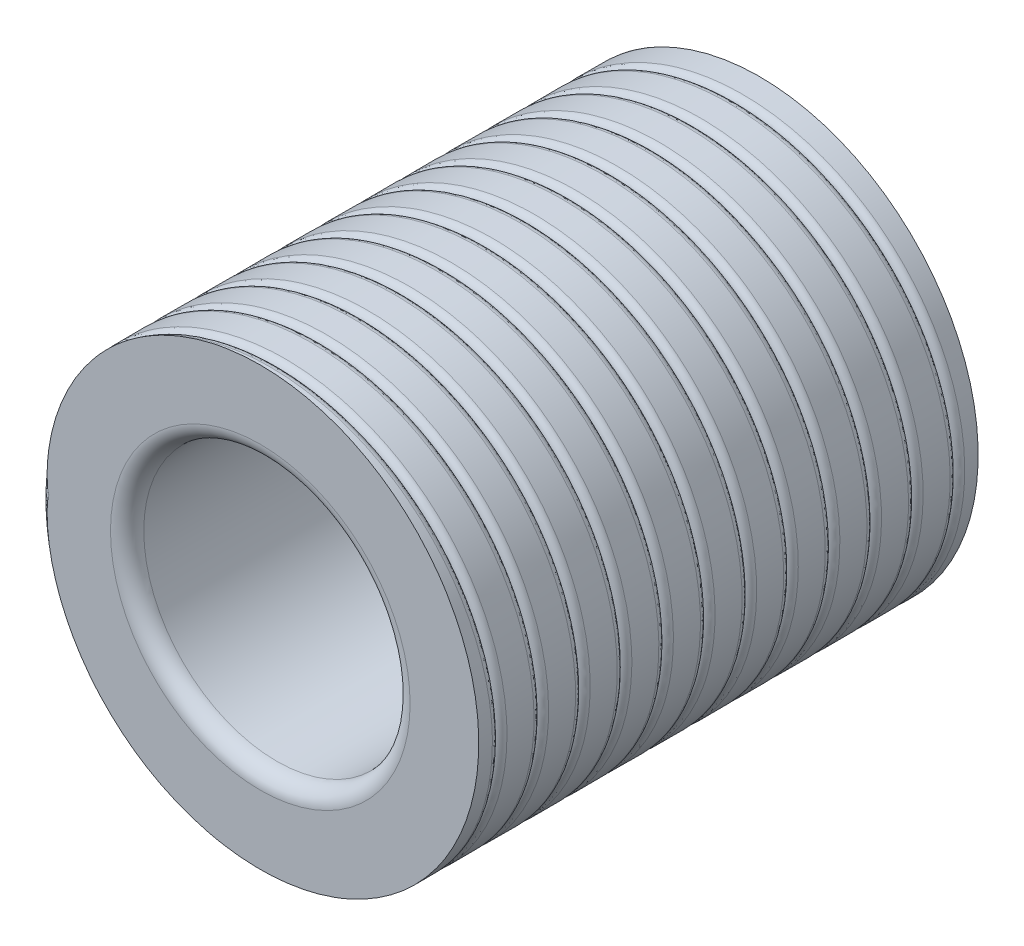
SolidWorks part; units mm, degrees
ref_plane "Front Plane" through (0, 0, 0) normal (0, 0, 1) x (1, 0, 0)
ref_plane "Top Plane" through (0, 0, 0) normal (0, 1, 0) x (1, 0, 0)
ref_plane "Right Plane" through (0, 0, 0) normal (1, 0, 0) x (0, 0, -1)
sketch "Sketch2" plane through (0, 0, 0) normal (0, 0, 1) x (1, 0, 0)
  circle A0 centre (0, 0) radius 6.4
  circle A1 centre (0, 0) radius 10.5
  dimension "D1" = 12.8
  dimension "D2" = 21
extrude "Boss-Extrude1" add sketch "Sketch2" along normal blind 24
fillet "Fillet1" radius 0.8 2 edges at (6.4, 0, 0) (6.4, 0, 24)
sketch "Sketch3" plane through (0, 0, 24) normal (0, 0, 1) x (1, 0, 0)
  circle A1 centre (0, 0) radius 10.5 construction
  circle A2 centre (0, 0) radius 10.5
curve "Helix/Spiral1" pitch 2 height 24 radius 10.5 centre (0, 0, 24) axis (0, 0, -1) start towards (-1, 0, 0)
sketch "Sketch4" plane through (0, 0, 0) normal (0, 1, 0) x (1, 0, 0)
  line L0 (-10.5, -24) -> (-10.5, -23.65)
  line L1 (-10.5, 0) -> (-10.5, -24) construction
  line L2 (-10.5, -24.35) -> (-10.5, -24)
  line L3 (-10.5, -24) -> (10.5, -24) construction
  arc A0 (-10.5, -23.65) -> (-10.15, -24) centre (-10.15, -23.65) ccw
  arc A1 (-10.15, -24) -> (-10.5, -24.35) centre (-10.15, -24.35) ccw
  dimension "D1" = 0.35
  dimension "D2" = 0.35
sweep "Cut-Sweep1" cut profiles "Sketch4" path "Helix/Spiral1" align with end faces yes
